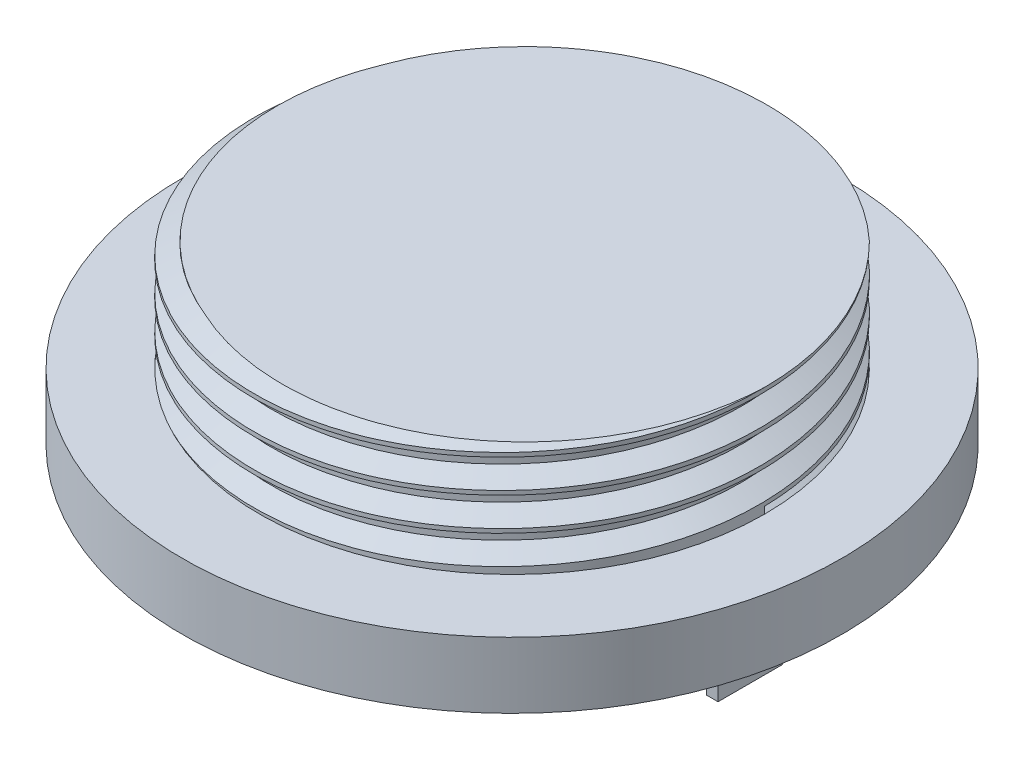
SolidWorks part; units mm, degrees
ref_plane "Alzado" through (0, 0, 0) normal (0, 0, 1) x (1, 0, 0)
ref_plane "Planta" through (0, 0, 0) normal (0, 1, 0) x (1, 0, 0)
ref_plane "Vista lateral" through (0, 0, 0) normal (1, 0, 0) x (0, 0, -1)
sketch "Croquis1" plane through (0, 0, 0) normal (0, 0, 1) x (1, 0, 0)
  line L0 (0, 0) -> (-11.5, 0)
  line L1 (-11.5, 0) -> (-11.5, -5)
  line L2 (-11.5, -5) -> (-15, -5)
  line L3 (-15, -5) -> (-15, -8)
  line L4 (-15, -8) -> (0, -8)
  line L5 (0, -8) -> (0, 0)
  dimension "D1" = 11.5
  dimension "D2" = 5
  dimension "D3" = 15
  dimension "D4" = 3
revolve "Revolución1" add sketch "Croquis1" angle 360 about L5
thread "Rosca1" pitch 1.5 start angle 0, offset 0, length 0, pitch 1.5, diameter 23
ref_plane "Plano1" through (11.5, 0, 0) normal (0, 0, 1) x (1, 0, 0)
sketch "Perfil de rosca1" plane through (11.5, 0, 0) normal (0, 0, 1) x (1, 0, 0)
  line L0 (0, 0) -> (0, 1.5) construction
  line L11 (0, 0) -> (0, 1.3125)
  line L12 (0, 1.3125) -> (-0.8119, 0.8437)
  line L13 (-0.8119, 0.8437) -> (-0.8119, 0.4687)
  line L15 (-0.8119, 0.4687) -> (0, 0)
  line L17 (-0.8119, 0.6562) -> (0, 0.6562) construction
  point P2 (0, 0)
  dimension "Pitch" = 1.5
  dimension "Profile_Angle" = 60
  dimension "Profile_Land" = 0.375
  dimension "Profile_Height" = 0.8119
sketch "Croquis4" plane through (0, -8, 0) normal (0, -1, 0) x (1, 0, 0)
  line L0 (-141.5039, -246.875) -> (-141.5039, -34.875) construction
  line L1 (-138.3656, -237.2134) -> (-138.3656, -25.2134) construction
  line L2 (7.0039, -3.9275) -> (5.6134, -3.4938)
  line L3 (12.8348, -3.2601) -> (12.8348, 0.4013) construction
  circle A0 centre (0, 0) radius 12.5 construction
  spline S0 degree 3 poles (10.9565, -6.0053) (10.5878, -6.1993) (9.8119, -5.7686) (9.0028, -5.5716) (8.3938, -5.3542) (7.9355, -5.1936) (7.5207, -5.166) (7.172, -5.159) (6.8839, -5.4989) (5.5613, -6.349) (1.6978, -7.9173) (-3.4629, -6.599) (-6.2859, -3.209) (-8.2409, 0.2404) (-9.6136, 3.2293) (-10.5993, 5.1623) knots 0 0 0 0 0.045509 0.074889 0.092461 0.113664 0.125695 0.137175 0.148043 0.170271 0.305001 0.581101 0.650984 0.7701 1 1 1 1
  spline S1 degree 3 poles (-10.5993, 5.1623) (-9.2315, 5.4325) (-6.53, 5.508) (-1.061, 5.442) (4.5752, 3.0946) (7.3672, -1.3197) (8.0556, -3.4383) (7.7947, -4.4942) (8.2038, -4.6057) (8.565, -4.773) (9.1184, -4.9513) (9.9134, -5.235) (11.0115, -5.4093) (10.9565, -6.0053) knots 0 0 0 0 0.154785 0.300688 0.611266 0.783841 0.856255 0.872093 0.881128 0.897547 0.918952 0.943746 1 1 1 1
  spline S2 degree 3 poles (6.3948, -4.8704) (5.9375, -5.409) (4.6239, -6.0027) (3.2746, -6.4992) (2.5192, -6.473) knots 0 0 0 0 0.481114 1 1 1 1
  spline S3 degree 1 poles (6.3948, -4.8704) (5.5853, -4.5093) knots 0 0 1 1
  spline S4 degree 3 poles (5.5853, -4.5093) (5.2482, -4.6994) (4.7712, -5.0734) (3.6999, -5.6505) (2.9394, -6.0097) (2.5192, -6.473) knots 0 0 0 0 0.317739 0.494985 1 1 1 1
  spline S5 degree 3 poles (7.0039, -3.9275) (7.0895, -3.348) (6.9581, -2.4677) (6.3352, -1.1307) (5.8533, -0.3804) (5.5175, 0.1263) knots 0 0 0 0 0.395874 0.586576 1 1 1 1
  spline S6 degree 3 poles (5.5175, 0.1263) (5.4236, -0.522) (5.5764, -1.7269) (5.5295, -2.9372) (5.6134, -3.4938) knots 0 0 0 0 0.536589 1 1 1 1
  spline S7 degree 3 poles (4.6653, -4.1147) (4.4089, -4.4755) (3.818, -4.8385) (3.0021, -5.4119) (2.1511, -5.8007) (1.6606, -6.2716) (1.3149, -6.401) knots 0 0 0 0 0.316444 0.507916 0.734242 1 1 1 1
  spline S8 degree 3 poles (1.3149, -6.401) (0.55, -6.5638) (-0.2449, -6.4329) (-0.9759, -6.1893) knots 0 0 0 0 1 1 1 1
  spline S9 degree 3 poles (-0.9759, -6.1893) (-0.6237, -5.8188) (0.0242, -5.3114) (0.9761, -4.6592) (1.8626, -4.0898) (2.4336, -3.6108) (2.7872, -3.4043) knots 0 0 0 0 0.326234 0.525 0.738479 1 1 1 1
  spline S10 degree 3 poles (4.6653, -4.1147) (4.3424, -4.0339) (3.7225, -3.7786) (3.1053, -3.5193) (2.7872, -3.4043) knots 0 0 0 0 0.495129 1 1 1 1
  spline S11 degree 3 poles (4.8926, -2.9359) (4.3204, -2.7716) (3.7703, -2.5399) (3.2299, -2.2924) knots 0 0 0 0 1 1 1 1
  spline S12 degree 3 poles (3.2299, -2.2924) (3.2421, -1.6407) (2.9689, -0.6289) (2.8823, 0.9616) (2.7612, 1.9006) (2.7872, 2.4539) knots 0 0 0 0 0.405946 0.652936 1 1 1 1
  spline S13 degree 3 poles (4.8926, -2.9359) (4.8594, -2.3938) (4.8015, -1.1659) (4.7274, 0.0613) (4.6653, 0.7448) knots 0 0 0 0 0.441733 1 1 1 1
  spline S14 degree 3 poles (4.6653, 0.7448) (4.588, 1.1064) (4.1826, 1.4842) (3.5867, 2.1329) (3.062, 2.2948) (2.7872, 2.4539) knots 0 0 0 0 0.397173 0.631475 1 1 1 1
  spline S15 degree 3 poles (1.7885, -2.9359) (1.3874, -3.2504) (0.7044, -3.7593) (-0.1444, -4.4928) (-1.0434, -4.9772) (-1.4957, -5.4903) (-1.8322, -5.7159) knots 0 0 0 0 0.334549 0.559859 0.734194 1 1 1 1
  spline S16 degree 3 poles (-1.8322, -5.7159) (-2.2798, -5.6948) (-2.8502, -5.2131) (-3.5275, -4.9111) (-3.7471, -4.6758) knots 0 0 0 0 0.568618 1 1 1 1
  spline S17 degree 3 poles (1.7885, -2.9359) (1.4325, -2.7288) (0.6075, -2.4742) (-0.0463, -1.9088) (-0.4168, -1.6854) knots 0 0 0 0 0.486655 1 1 1 1
  spline S18 degree 3 poles (-3.7471, -4.6758) (-3.4062, -4.3393) (-2.4009, -3.2267) (-1.1061, -2.4339) (-0.4168, -1.6854) knots 0 0 0 0 0.321358 1 1 1 1
  spline S19 degree 3 poles (-1.4732, -1.225) (-1.6748, -1.6859) (-2.2858, -2.186) (-3.4082, -3.0027) (-3.8741, -3.8127) (-4.4186, -4.1147) knots 0 0 0 0 0.350602 0.564021 1 1 1 1
  spline S20 degree 3 poles (-4.4186, -4.1147) (-4.8257, -3.8494) (-5.2166, -3.0785) (-5.8128, -2.4659) (-6.014, -2.1371) knots 0 0 0 0 0.548239 1 1 1 1
  spline S21 degree 3 poles (-6.014, -2.1371) (-5.5532, -1.8424) (-4.9061, -1.4277) (-3.9949, -0.7331) (-3.4514, -0.4619) (-3.1913, -0.1818) knots 0 0 0 0 0.477748 0.66972 1 1 1 1
  spline S22 degree 3 poles (-1.4732, -1.225) (-1.9974, -0.7918) (-2.6981, -0.6586) (-3.1913, -0.1818) knots 0 0 0 0 1 1 1 1
  spline S23 degree 3 poles (-6.3896, -1.5035) (-5.9306, -1.0525) (-5.0437, -0.7021) (-4.1675, -0.0864) (-4.0436, 0.2809) knots 0 0 0 0 0.616737 1 1 1 1
  spline S24 degree 3 poles (-6.3896, -1.5035) (-6.7758, -1.0656) (-7.0301, -0.1277) (-7.584, 0.6554) (-7.7574, 0.9965) knots 0 0 0 0 0.597562 1 1 1 1
  spline S25 degree 3 poles (-7.7574, 0.9965) (-7.1806, 1.0461) (-6.9001, 1.8869) (-6.29, 1.7383) knots 0 0 0 0 1 1 1 1
  spline S26 degree 3 poles (-4.0436, 0.2809) (-4.7008, 0.9175) (-5.6478, 1.0804) (-6.29, 1.7383) knots 0 0 0 0 1 1 1 1
  spline S27 degree 3 poles (-7.0961, 2.2943) (-7.2876, 2.2196) (-7.8519, 1.4527) (-8.3353, 2.0252) (-8.6641, 2.7416) (-9.0212, 3.3922) (-9.261, 3.8497) knots 0 0 0 0 0.310868 0.394958 0.558357 1 1 1 1
  spline S28 degree 3 poles (-7.0961, 2.2943) (-7.3945, 2.5753) (-8.0953, 3.1243) (-8.8019, 3.6789) (-9.261, 3.8497) knots 0 0 0 0 0.458358 1 1 1 1
  spline S29 degree 3 poles (-6.915, 3.3968) (-6.8892, 3.7393) (-6.9351, 4.0773) (-6.896, 4.7745) (-7.3048, 4.7637) (-7.6577, 4.8462) (-8.3003, 4.7736) (-8.7851, 4.9476) (-9.1251, 4.837) knots 0 0 0 0 0.268265 0.385213 0.459279 0.566834 0.712658 1 1 1 1
  spline S30 degree 3 poles (-6.915, 3.3968) (-7.3252, 3.6435) (-8.0867, 4.0897) (-8.7608, 4.6614) (-9.1251, 4.837) knots 0 0 0 0 0.544609 1 1 1 1
  spline S31 degree 3 poles (-3.8143, 1.4186) (-4.2735, 1.5667) (-4.7522, 2.0802) (-5.6293, 2.3387) (-5.9145, 2.9468) (-6.0365, 3.7161) (-6.1232, 4.3456) (-6.1233, 4.7283) knots 0 0 0 0 0.312979 0.470055 0.574114 0.74199 1 1 1 1
  spline S32 degree 3 poles (-3.8143, 1.4186) (-4.0045, 1.959) (-3.9137, 2.7524) (-4.2175, 3.7193) (-4.4038, 4.2084) (-4.4882, 4.6738) (-5.1814, 4.8146) (-5.6521, 4.6562) (-6.1233, 4.7283) knots 0 0 0 0 0.341457 0.475561 0.607155 0.678259 0.727851 1 1 1 1
  spline S33 degree 3 poles (-1.3498, 0) (-1.7147, 0.1988) (-2.1988, 0.4075) (-2.7779, 0.8015) (-3.0486, 1.3445) (-3.226, 2.0716) (-3.1986, 3.2296) (-3.6544, 3.9878) (-3.6559, 4.5472) knots 0 0 0 0 0.225465 0.291568 0.375328 0.547817 0.698545 1 1 1 1
  spline S34 degree 3 poles (-1.3498, 0) (-1.3516, 0.5497) (-1.6922, 1.3342) (-1.731, 2.4309) (-1.9102, 3.2413) (-1.9911, 3.8352) (-2.0504, 4.4285) (-2.8246, 4.468) (-3.2298, 4.6273) (-3.6559, 4.5472) knots 0 0 0 0 0.271622 0.416103 0.548394 0.680553 0.734696 0.811447 1 1 1 1
  spline S35 degree 3 poles (2.226, -1.6854) (1.806, -1.5426) (1.0911, -1.3629) (0.3255, -0.8208) (-0.3221, -0.6429) (-0.6815, 0.066) (-0.6555, 0.9516) (-1.0225, 2.327) (-0.9416, 3.3638) (-1.1416, 4.0173) knots 0 0 0 0 0.180625 0.286973 0.37907 0.43135 0.590976 0.729094 1 1 1 1
  spline S36 degree 3 poles (2.226, -1.6854) (2.2504, -1.1188) (2.1423, -0.2333) (2.0385, 1.0758) (1.81, 2.0438) (1.9848, 3.0174) (1.3654, 3.3908) (0.7928, 3.6083) (-0.0986, 3.793) (-0.7055, 4.1234) (-1.1416, 4.0173) knots 0 0 0 0 0.213489 0.340134 0.492639 0.605071 0.657073 0.746886 0.84184 1 1 1 1
  text T0 "LL" font "Unispace" height in points 16
  dimension "D1" = 25
extrude "Saliente-Extruir1" add sketch "Croquis4" along normal blind 2
